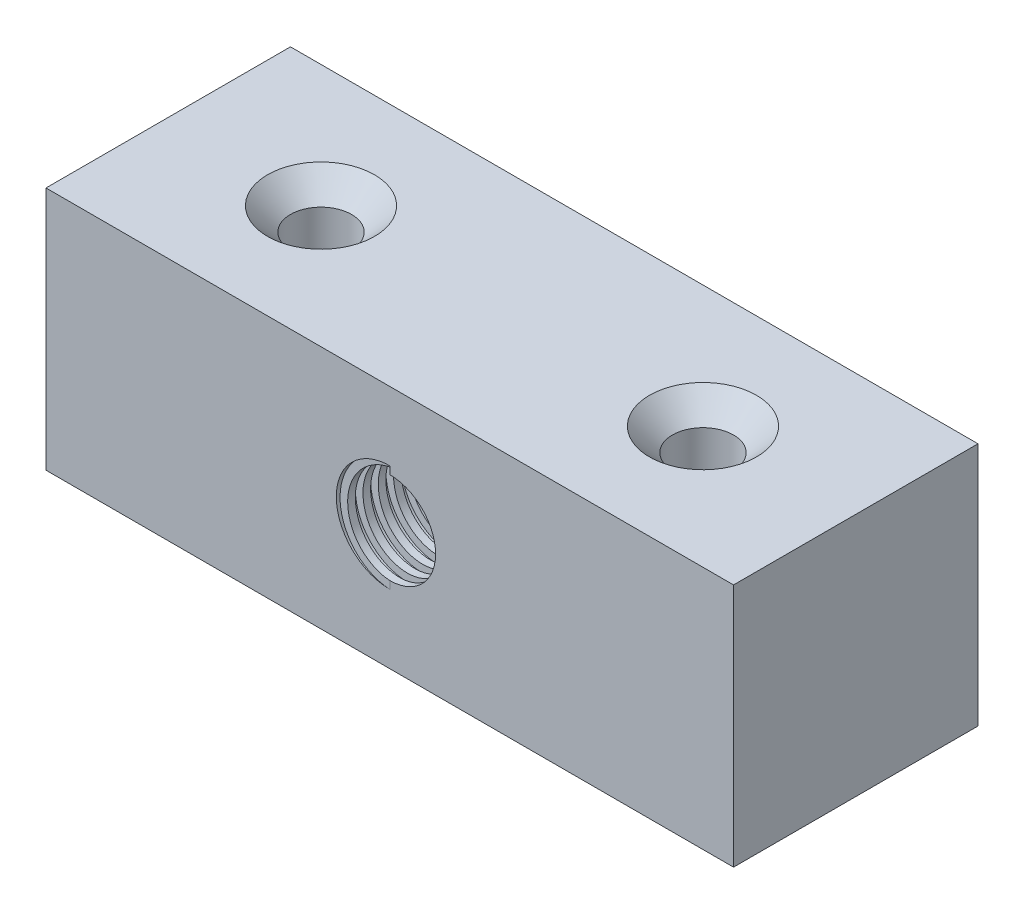
SolidWorks part; units mm, degrees
ref_plane "Front Plane" through (0, 0, 0) normal (0, 0, 1) x (1, 0, 0)
ref_plane "Top Plane" through (0, 0, 0) normal (0, 1, 0) x (1, 0, 0)
ref_plane "Right Plane" through (0, 0, 0) normal (1, 0, 0) x (0, 0, -1)
sketch "Sketch1" plane through (0, 0, 0) normal (0, 0, 1) x (1, 0, 0)
  line L1 (-45, -16) -> (45, -16)
  line L2 (-45, -16) -> (-45, 16)
  line L3 (-45, 16) -> (45, 16)
  line L4 (45, -16) -> (45, 16)
  line L5 (-45, -16) -> (45, 16) construction
  line L6 (-45, 16) -> (45, -16) construction
  point P0 (0, 0)
  dimension "D1" = 90
  dimension "D2" = 32
extrude "Boss-Extrude1" add sketch "Sketch1" along normal mid plane 32
sketch "Sketch2" plane through (45, 0, 0) normal (1, 0, 0) x (0, 0, -1)
  line L0 (-16, 6.5) -> (-9.5, 0)
  line L1 (-16, -16) -> (-16, 16) construction
  line L2 (-9.5, 0) -> (-16, -6.5)
  line L3 (0, 0) -> (-7.5607, 0) construction
  line L4 (-16, 6.5) -> (-16, -6.5)
  dimension "D1" = 13
  dimension "D2" = 90
extrude "Cut-Extrude1" [suppressed] cut sketch "Sketch2" against normal through all
hole_wizard "Ø8.0mm Dowel Hole1" positions "Sketch3" profile "Sketch5" hole size "Ø8.0" standard "ISO" end condition up to next
sketch "Sketch3" plane through (0, 16, 0) normal (0, 1, 0) x (1, 0, 0)
  line L0 (0, 0) -> (0, 12.1265) construction
  point P0 (-25, 0)
  point P2 (25, 0)
  dimension "D1" = 50
sketch "Sketch5" plane through (-25, 16, 0) normal (1, 0, 0) x (0, 0, 1)
  line L0 (0, 0) -> (0, 32)
  line L1 (0, 32) -> (4, 32)
  line L2 (4, 32) -> (4, 0)
  line L5 (4, 0) -> (0, 0)
  line L11 (0, -6.35) -> (0, 107.95) construction
  dimension "Thru Hole Dia." = 8
  dimension "Thru Hole Depth" = 32
chamfer "Chamfer1" distance 3 angle 45 2 edges at (25, 16, 4) (-25, 16, 4)
hole_wizard "Ø12.0mm Dowel Hole1" positions "Sketch6" profile "Sketch7" hole size "Ø12.0" standard "ISO" end condition up to next
sketch "Sketch6" plane through (0, 0, -16) normal (0, 0, -1) x (-1, 0, 0)
  point P0 (0, 0)
sketch "Sketch7" plane through (0, 0, -16) normal (1, 0, 0) x (0, 1, 0)
  line L0 (0, 0) -> (0, 32)
  line L1 (0, 32) -> (6, 32)
  line L2 (6, 32) -> (6, 0)
  line L5 (6, 0) -> (0, 0)
  line L11 (0, -6.35) -> (0, 107.95) construction
  dimension "Thru Hole Dia." = 12
  dimension "Thru Hole Depth" = 32
sketch "Sketch8" plane through (0, 0, -16) normal (0, 0, -1) x (-1, 0, 0)
  circle A0 centre (0, 0) radius 6 construction
  circle A1 centre (0, 0) radius 6
curve "Helix/Spiral1" pitch 2 height 34.5 turns 17.25
ref_plane "Plane2" through (-6, 0, -16) normal (0, -0.9986, 0.053) x (-1, 0, 0)
sketch "Sketch10" plane through (-6, 0, -16) normal (0, -0.9986, 0.053) x (-1, 0, 0)
  line L1 (-1, -0.5) -> (1, -0.5)
  line L2 (-1, -0.5) -> (-1, 0.5)
  line L3 (-1, 0.5) -> (1, 0.5)
  line L4 (1, -0.5) -> (1, 0.5)
  line L5 (-1, -0.5) -> (1, 0.5) construction
  line L6 (-1, 0.5) -> (1, -0.5) construction
  point P0 (0, 0)
  point P5 (0, 0)
  point P6 (0.6917, 0.0725)
  dimension "D1" = 2
  dimension "D2" = 1
sweep "Cut-Sweep5" cut profiles "Sketch10" path "Helix/Spiral1"
